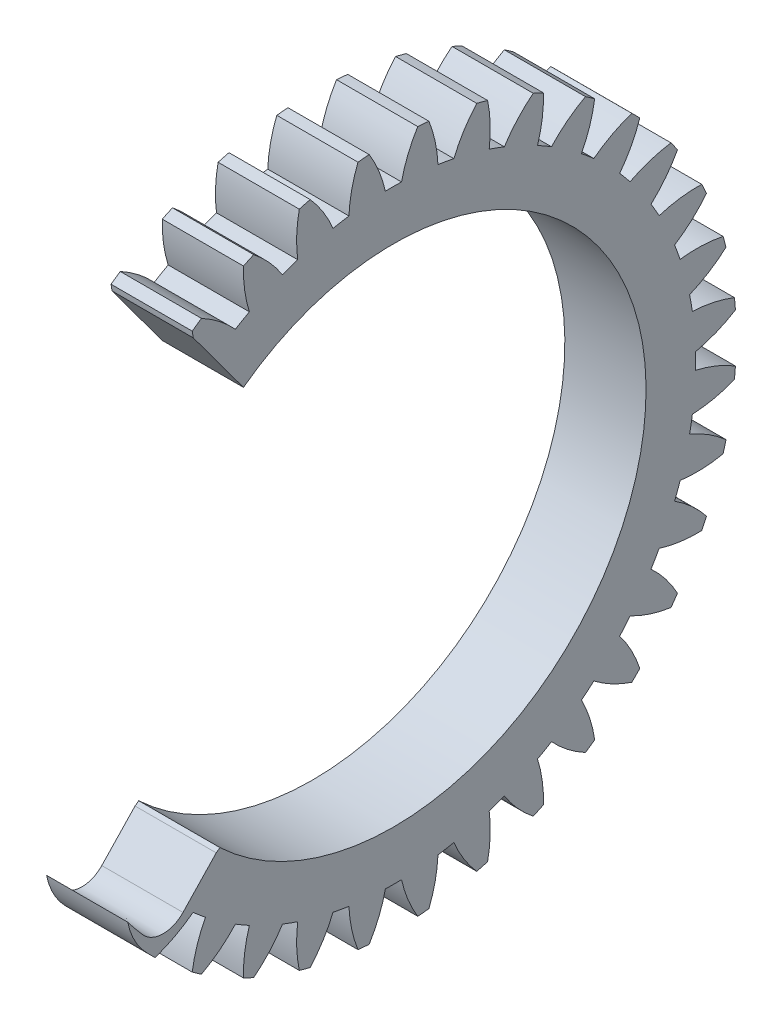
SolidWorks part; units mm, degrees
ref_plane "Plane1" through (0, 0, 0) normal (0, 0, 1) x (1, 0, 0)
ref_plane "Plane2" through (0, 0, 0) normal (0, 1, 0) x (1, 0, 0)
ref_plane "Plane3" through (0, 0, 0) normal (1, 0, 0) x (0, 0, -1)
sketch "HoldingSke" plane through (0, 0, 0) normal (0, 1, 0) x (1, 0, 0)
  line L0 (0, 0) -> (0.4045, -0.2939)
  line L1 (-15, 0) -> (100, 0) construction
  line L2 (0, 0) -> (-2.1039, 2.3779)
  line L3 (0, 0) -> (-11.863, 4.5341)
  line L4 (0, 0) -> (6.9867, 5.0761)
  line L5 (0, 0) -> (-46.8476, -17.4728)
  line L6 (0, 0) -> (-7.4607, -5.0337)
  line L7 (-2.1039, 2.3779) -> (8.6586, 51.2059)
  line L8 (-76.2, 54.61) -> (-71.9, 54.61)
  line L9 (-71.009, 38.7566) -> (-53.1078, 45.2721)
  line L10 (-76.2, 71.12) -> (104.1128, 71.12)
  line L11 (0, 0) -> (-9, 0)
  line L12 (-76.2, 101.6) -> (-76.133, 101.6)
  line L13 (24.9733, 27.94) -> (52.9518, 28.4284)
  line L14 (24.9733, 27.94) -> (24.9743, 27.94)
  line L15 (24.9733, 27.94) -> (100.4006, 29.5858)
  line L16 (-63.627, -2) -> (-12.827, -2)
  circle A0 centre (0, 0) radius 28
  circle A1 centre (0, 0) radius 33.499
  circle A2 centre (0, 0) radius 37.5
  circle A3 centre (0, 0) radius 28
  dimension "Num_teeth" = 36
  dimension "Pitch_radius" = 180.3128
  dimension "Width" = 9
  dimension "Thickness" = 9
sketch "BasProSke" plane through (0, 0, 0) normal (0, 1, 0) x (1, 0, 0)
  line L0 (-10, 0) -> (60, 0) construction
  line L1 (0, 0) -> (0, 38)
  line L2 (0, 0) -> (9, 0)
  line L3 (9, 0) -> (9, 38)
  line L4 (9, 38) -> (0, 38)
  dimension "Thickness" = 9
  dimension "Diameter" = 76
revolve "Base-Revolve" add sketch "BasProSke" angle 360 about L0
sketch "TooCutSke" plane through (0, 0, 0) normal (1, 0, 0) x (0, 0, -1)
  line L1 (0, 0) -> (0, 107) construction
  line L2 (0, 0) -> (-1.6875, 35.9604) construction
  line L3 (0, 0) -> (-6.2701, 71.6676) construction
  line L4 (-1.6875, 35.9604) -> (-3.135, 35.8338) construction
  arc A0 (0.8949, 33.487) -> (-0.8949, 33.487) centre (0, 0) ccw
  arc A1 (2.7061, 37.929) -> (-2.7061, 37.929) centre (0, 0) ccw
  circle A2 centre (0, 0) radius 36 construction
  circle A3 centre (0, 0) radius 33.8289 construction
  arc A4 (-0.8949, 33.487) -> (-2.7061, 37.929) centre (-14.9484, 30.347) ccw
  arc A5 (2.7061, 37.929) -> (0.8949, 33.487) centre (14.9484, 30.347) ccw
extrude "ToothCut" cut sketch "TooCutSke" along normal through all
fillet "Breaks" [suppressed] radius 0.04 tangent propagation no
fillet "RootFillets" [suppressed] radius 0.501
pattern_circular "TeethCuts" count 36 every 10 about axis through (-10, 0, 0) along (1, 0, 0) of "ToothCut", "RootFillets", "Breaks"
sketch "HubNeaOneSke" plane through (0, 0, 0) normal (-1, 0, 0) x (0, 0, 1)
  circle A0 centre (0, 0) radius 33.499
  dimension "Diameter" = 66.998
extrude "HubNearOne" [suppressed] add sketch "HubNeaOneSke" along normal blind 41.0001
sketch "HubNeaBotSke" plane through (0, 0, 0) normal (-1, 0, 0) x (0, 0, 1)
  circle A0 centre (0, 0) radius 33.499
  dimension "Diameter" = 66.998
extrude "HubNearBoth" [suppressed] add sketch "HubNeaBotSke" along normal blind 20.5
ref_plane "FarPln" through (9, 0, 0) normal (1, 0, 0) x (0, 0, -1)
sketch "HubFarSke" plane through (9, 0, 0) normal (1, 0, 0) x (0, 0, -1)
  circle A0 centre (0, 0) radius 33.499
  dimension "Diameter" = 66.998
extrude "HubFar" [suppressed] add sketch "HubFarSke" along normal blind 20.5
sketch "BorSke" plane through (0, 0, 0) normal (1, 0, 0) x (0, 0, -1)
  circle A0 centre (0, 0) radius 28
  dimension "Diameter" = 56
extrude "Bore" cut sketch "BorSke" along normal mid plane 100.0001
sketch "KeySke" plane through (0, 0, 0) normal (1, 0, 0) x (0, 0, -1)
  line L0 (-8, 0) -> (-8, 32.3)
  line L1 (-8, 32.3) -> (8, 32.3)
  line L2 (8, 32.3) -> (8, 0)
  line L3 (0, 0) -> (0, 34) construction
  line L4 (-8, 0) -> (8, 0)
  dimension "Width" = 16
extrude "Keyway" [suppressed] cut sketch "KeySke" along normal mid plane 100.0001
pattern_circular "Keyway2" [suppressed] count 2 every 90 about axis through (-10, 0, 0) along (1, 0, 0) reverse direction yes
sketch "Szkic1" plane through (0, 0, 0) normal (1, 0, 0) x (0, 0, -1)
  line L0 (0, 0) -> (-27.328, 37.0259)
  line L1 (-27.328, 37.0259) -> (-47.6164, -10.233)
  line L2 (-47.6164, -10.233) -> (0, 0)
extrude "Wytnij-wyciągnięcie1" cut sketch "Szkic1" along normal through all
sketch "Szkic2" plane through (0, 0, 0) normal (1, 0, 0) x (0, 0, -1)
  line L0 (-19.6433, -20.6493) -> (-23.3286, -24.5233) construction
  line L1 (-19.6433, -20.6493) -> (-23.3286, -24.5233)
  line L2 (-24.5118, 27.7159) -> (-14.2182, -16.6493)
  line L3 (-14.2182, -16.6493) -> (-19.6433, -20.6493)
  line L4 (-24.5118, 27.7159) -> (-50.9594, 25.255)
  line L5 (-50.9594, 25.255) -> (-37.7356, -29.3697)
  line L6 (-37.7356, -29.3697) -> (-27.7664, -24.4546)
  line L7 (-26.426, -27.3069) -> (-27.3069, -26.426)
  line L8 (-26.426, -27.3069) -> (-25.0675, -25.4318)
  arc A0 (-24.5118, 27.7159) -> (-27.7664, -24.4546) centre (0, 0) ccw construction
  arc A1 (-24.5118, 27.7159) -> (-27.7664, -24.4546) centre (0, 0) ccw
  arc A2 (-27.3069, -26.426) -> (-29.4473, -22.4022) centre (-21.7924, -20.9115) cw
  spline S0 degree 3 poles (316223.8882, 391931.8645) (8405.0036, 10934.5641) (-161.0339, 74.5996) (-27.1426, -24.9996) (-26.9606, -25.1074) (-26.5829, -25.2806) (-26.3868, -25.3469) (-25.9801, -25.4387) (-25.7711, -25.4633) (-25.3572, -25.469) (-25.1483, -25.4503) (-24.7384, -25.37) (-24.5404, -25.3094) (-24.158, -25.1482) (-23.9725, -25.0463) (123.8715, 77.2174) (-9306.9461, 12697.8841) (-305756.1415, 400434.5891) knots -100.461167 -100.461167 -100.461167 -100.461167 0.125 0.125 0.25 0.25 0.375 0.375 0.5 0.5 0.625 0.625 0.75 0.75 0.875 0.875 109.018939 109.018939 109.018939 109.018939 only from (-27.7664, -24.4546) to (-23.3286, -24.5233) construction
  spline S1 degree 3 poles (-27.7664, -24.4546) (-27.6277, -24.6121) (-27.4749, -24.7523) (-27.1426, -24.9996) (-26.9606, -25.1074) (-26.5829, -25.2806) (-26.3868, -25.3469) (-25.9801, -25.4387) (-25.7711, -25.4633) (-25.3572, -25.469) (-25.1483, -25.4503) (-24.7384, -25.37) (-24.5404, -25.3094) (-24.158, -25.1482) (-23.9725, -25.0463) (-23.6312, -24.8102) (-23.4733, -24.6754) (-23.3286, -24.5233) knots 0 0 0 0 0.125 0.125 0.25 0.25 0.375 0.375 0.5 0.5 0.625 0.625 0.75 0.75 0.875 0.875 1 1 1 1
extrude "Wytnij-wyciągnięcie2" cut sketch "Szkic2" against normal blind 43 and the other way through all contours A1 L4 L5 L6 | A1 S1 L1 L3 L2 region at (0, -1.5762, 26.5296) region at (0, 4.8425, 39.1923)
extrude "Dodanie-wyciągnięcie1" add sketch "Szkic2<3>" along normal up to surface (9 mm away) contours A2 L6 A1 | S1 L6 A2 L7 L8 region at (0, -25.7946, 26.8655) region at (0, -23.8723, 28.649) up to face at (9, -1.2954, -9.9994)
sketch "Szkic2<3>" plane through (0, 0, 0) normal (1, 0, 0) x (0, 0, -1) same geometry as "Szkic2"
equation "' \"Module@HoldingSke\" = 6.35"
equation "' \"Num_teeth@HoldingSke\" = 12"
equation "' \"Ap@HoldingSke\" =  20"
equation "' \"Ap@HoldingSke\" = 20"
equation "' \"Width@HoldingSke\" = 0.5 * 25.4"
equation "' \"Hub_dia@HoldingSke\"= 1 * 25.4"
equation "' \"Hub_dia@HoldingSke\" = 1 * 25.4"
equation "' \"Overall_len@HoldingSke\" = 1.0 * 25.4"
equation "' \"Bore@HoldingSke\" = 0.75 * 25.4"
equation "' \"T_dim@HoldingSke\" = 0.1 * 25.4"
equation "' \"Width@KeySke\" = 0.25 * 25.4"
equation "' \"Show_teeth@HoldingSke\" = 13"
equation "' \"Backlash@HoldingSke\" = 0.009 * 25.4"
equation "' \"Addendum_fac@HoldingSke\" = 1.0"
equation "' \"Dedendum_fac@HoldingSke\" = 1.25"
equation "' \"Dedendum_add@HoldingSke\" = 0.00005 * 25.4"
equation "' \"Clearance_fac@HoldingSke\" = 0.25"
equation "\"Pitch@HoldingSke\" = 1 / \"Module@HoldingSke\""
equation "\"Overcut_dia@TooCutSke\" = (\"Num_teeth@HoldingSke\" + 2 * \"Addendum_fac@HoldingSke\") / \"Pitch@HoldingSke\" + 0.002 * 25.4"
equation "\"Pitch_dia@TooCutSke\" = \"Num_teeth@HoldingSke\" / \"Pitch@HoldingSke\""
equation "\"Base_dia@TooCutSke\" = \"Num_teeth@HoldingSke\" / \"Pitch@HoldingSke\" * cos((\"Ap@HoldingSke\"  * 3.14159265 / 180))"
equation "\"Root_dia@TooCutSke\" = (\"Num_teeth@HoldingSke\" + 2) / \"Pitch@HoldingSke\" - 2 * (\"Addendum_fac@HoldingSke\" + \"Dedendum_fac@HoldingSke\") / \"Pitch@HoldingSke\" - \"Dedendum_add@HoldingSke\" * 2"
equation "\"Half_ang@TooCutSke\" = 180 / \"Num_teeth@HoldingSke\""
equation "\"Half_CT@TooCutSke\" = \"Num_teeth@HoldingSke\" / \"Pitch@HoldingSke\" * sin((3.14159265 / 2 / \"Num_teeth@HoldingSke\")) / 2 - 7 * \"Backlash@HoldingSke\" / 4"
equation "\"Flank_rad@TooCutSke\" = \"Num_teeth@HoldingSke\" / \"Pitch@HoldingSke\" / 5"
equation "\"Radius@RootFillets\" = \"Clearance_fac@HoldingSke\" / \"Pitch@HoldingSke\" + \"Dedendum_add@HoldingSke\""
equation "\"Break_rad@Breaks\" = 0.02 / \"Pitch@HoldingSke\""
equation "\"Thickness@HoldingSke\" = \"Width@HoldingSke\""
equation "\"OAL@HoldingSke\" = \"Thickness@HoldingSke\""
equation "\"MHD@HoldingSke\" = (\"Num_teeth@HoldingSke\" + 2) / \"Pitch@HoldingSke\" - 2 * (\"Addendum_fac@HoldingSke\" + \"Dedendum_fac@HoldingSke\")  / \"Pitch@HoldingSke\" - \"Dedendum_add@HoldingSke\" * 2"
equation "\"MBD@HoldingSke\" = (\"Num_teeth@HoldingSke\" + 2) / \"Pitch@HoldingSke\" - 2 * (\"Addendum_fac@HoldingSke\" + \"Dedendum_fac@HoldingSke\")  / \"Pitch@HoldingSke\" - \"Dedendum_add@HoldingSke\" * 2 - 0.002 * 25.4"
equation "\"MHD@HoldingSke\" = ((sgn( \"MHD@HoldingSke\" - \"Hub_dia@HoldingSke\" )-1)*( \"MHD@HoldingSke\" - \"Hub_dia@HoldingSke\" ))/-2+ \"Hub_dia@HoldingSke\""
equation "\"MBD@HoldingSke\" = ((sgn( \"MBD@HoldingSke\" - \"Bore@HoldingSke\" )-1)*( \"MBD@HoldingSke\" - \"Bore@HoldingSke\" ))/-2+ \"Bore@HoldingSke\""
equation "\"OAL@HoldingSke\" = ((sgn( \"OAL@HoldingSke\" - \"Overall_len@HoldingSke\" )+1)*( \"OAL@HoldingSke\" - \"Overall_len@HoldingSke\" ))/2 + \"Overall_len@HoldingSke\" + 0.000002 * 25.4"
equation "\"Num_teeth@TeethCuts\" = int( \"Show_teeth@HoldingSke\" ) + 1"
equation "\"Num_teeth@TeethCuts\" = ((sgn( \"Num_teeth@TeethCuts\" - \"Num_teeth@HoldingSke\" )-1)*( \"Num_teeth@TeethCuts\" - \"Num_teeth@HoldingSke\" ))/-2+ \"Num_teeth@HoldingSke\""
equation "\"Num_teeth@TeethCuts\" = ((sgn( \"Num_teeth@TeethCuts\" - 2.0)+1)*( \"Num_teeth@TeethCuts\" - 2.0))/2 +2.0"
equation "\"Angle@TeethCuts\" = 360.0 / \"Num_teeth@HoldingSke\""
equation "\"Diameter@BasProSke\" = (\"Num_teeth@HoldingSke\" + 2 * \"Addendum_fac@HoldingSke\") / \"Pitch@HoldingSke\""
equation "\"Thickness@BasProSke\"  = \"Thickness@HoldingSke\""
equation "' \"Fillet_rad@BasProSke\" =  \"Thickness@HoldingSke\" * 0.05"
equation "' \"Fillet_rad@BasProSke\" = \"Thickness@HoldingSke\" * 0.05"
equation "\"MHD@HoldingSke\" = ((sgn( \"MHD@HoldingSke\" - \"Root_dia@TooCutSke\" )-1)*( \"MHD@HoldingSke\" - \"Root_dia@TooCutSke\" ))/-2+ \"Root_dia@TooCutSke\""
equation "\"Diameter@HubNeaOneSke\" = \"MHD@HoldingSke\""
equation "\"Length@HubNearOne\" = \"OAL@HoldingSke\" - \"Thickness@BasProSke\""
equation "\"Diameter@HubNeaBotSke\" = \"MHD@HoldingSke\""
equation "\"Length@HubNearBoth\" = ( \"OAL@HoldingSke\" - \"Thickness@BasProSke\" ) / 2.0"
equation "\"Thickness@FarPln\" = \"Thickness@BasProSke\""
equation "\"Diameter@HubFarSke\" = \"MHD@HoldingSke\""
equation "\"Length@HubFar\" = ( \"OAL@HoldingSke\" - \"Thickness@BasProSke\" ) / 2.0"
equation "\"Diameter@BorSke\" = \"MBD@HoldingSke\""
equation "\"D1@Bore\" = \"OAL@HoldingSke\" * 2.0"
equation "\"D1@Keyway\" = \"OAL@HoldingSke\" * 2.0"
equation "\"Offset@KeySke\" = \"T_dim@HoldingSke\" + \"MBD@HoldingSke\" / 2.0"
